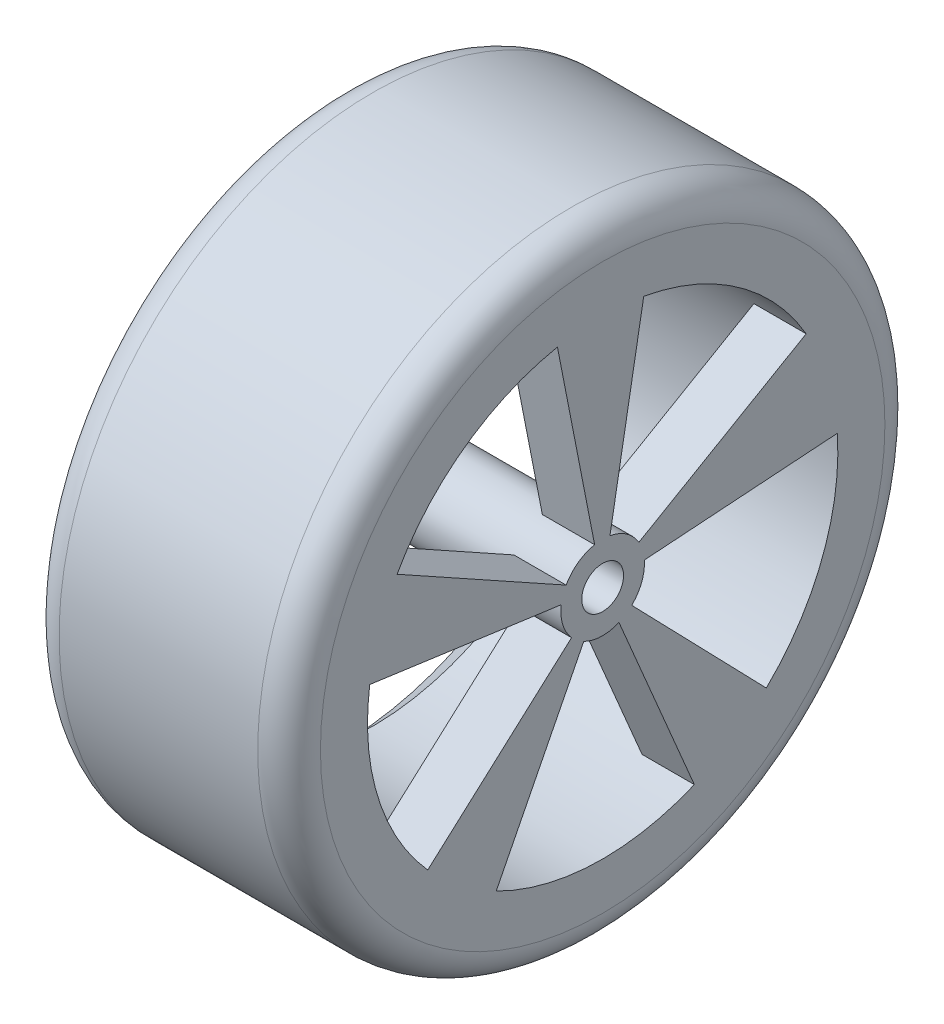
SolidWorks part; units mm, degrees
ref_plane "Front Plane" through (0, 0, 0) normal (0, 0, 1) x (1, 0, 0)
ref_plane "Top Plane" through (0, 0, 0) normal (0, 1, 0) x (1, 0, 0)
ref_plane "Right Plane" through (0, 0, 0) normal (1, 0, 0) x (0, 0, -1)
sketch "Sketch1" plane through (0, 0, 0) normal (1, 0, 0) x (0, 0, -1)
  circle A0 centre (0, 0) radius 30
  dimension "D1" = 60
extrude "Boss-Extrude1" add sketch "Sketch1" along normal blind 25
fillet "Fillet1" radius 3 2 edges at (0, 0, -30) (25, 0, -30)
sketch "Sketch3" plane through (0, 0, 0) normal (-1, 0, 0) x (0, 0, 1)
  circle A0 centre (0, 0) radius 22.5
  dimension "D1" = 45
extrude "Cut-Extrude1" cut sketch "Sketch3" against normal blind 20
chamfer "Chamfer1" distance 3 angle 45 1 edges at (0, 0, 22.5)
sketch "Sketch2" plane through (25, 0, 0) normal (-1, 0, 0) x (0, 0, 1)
  line L0 (-0.6984, 3.9386) -> (-3.9284, 22.1544)
  line L1 (-3.461, 2.0054) -> (-19.4681, 11.2803)
  arc A0 (-0.6984, 3.9386) -> (-3.461, 2.0054) centre (0, 0) ccw
  arc A1 (-3.9284, 22.1544) -> (-19.4681, 11.2803) centre (0, 0) ccw
  dimension "D1" = 8
  dimension "D2" = 45
extrude "Cut-Extrude2" cut sketch "Sketch2" along normal through all
pattern_circular "CirPattern1" count 5 every 71 about axis through (25, 0, 0) along (1, 0, 0) of "Cut-Extrude2"
sketch "Sketch4" plane through (20, 0, 0) normal (-1, 0, 0) x (0, 0, 1)
  circle A0 centre (0, 0) radius 4
extrude "Boss-Extrude2" add sketch "Sketch4" along normal blind 15
sketch "Sketch5" plane through (5, 0, 0) normal (-1, 0, 0) x (0, 0, 1)
  circle A0 centre (0, 0) radius 2
  dimension "D1" = 4
extrude "Cut-Extrude3" cut sketch "Sketch5" against normal through all
